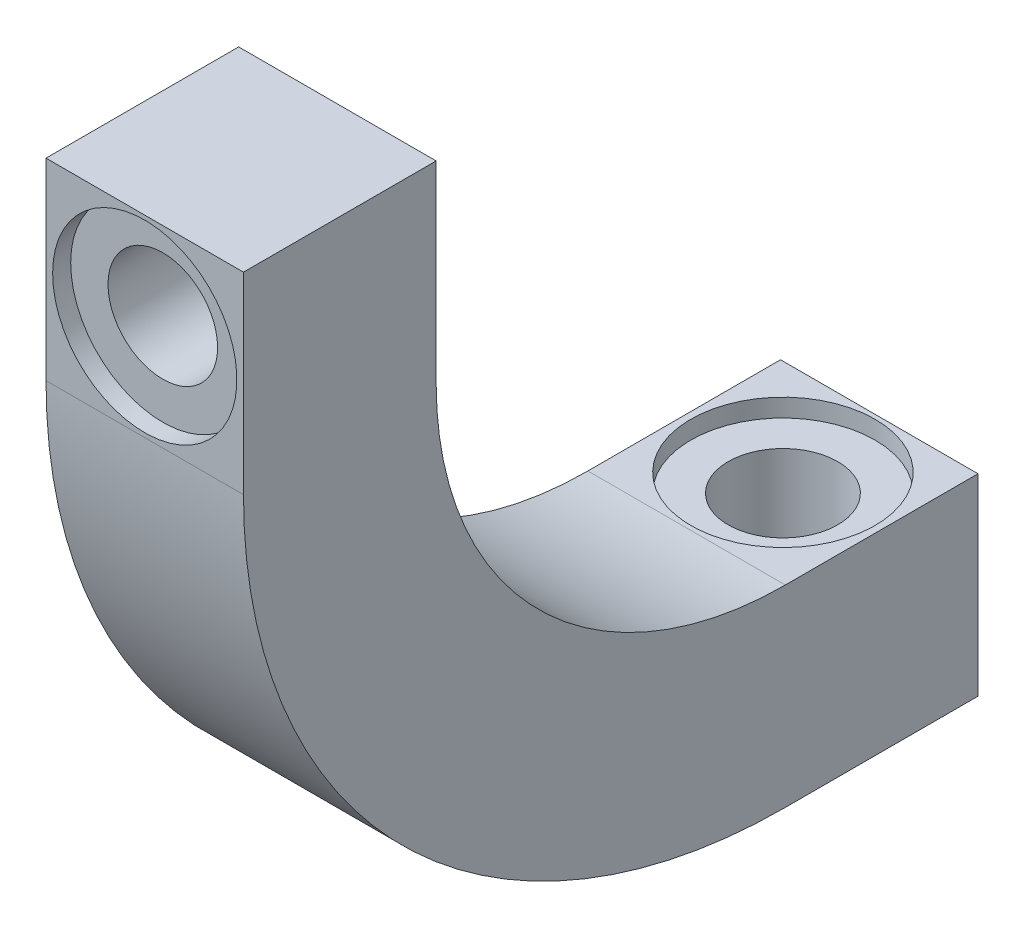
SolidWorks part; units mm, degrees
ref_plane "Front Plane" through (0, 0, 0) normal (0, 0, 1) x (1, 0, 0)
ref_plane "Top Plane" through (0, 0, 0) normal (0, 1, 0) x (1, 0, 0)
ref_plane "Right Plane" through (0, 0, 0) normal (1, 0, 0) x (0, 0, -1)
ref_axis "Z" through (0, 0, 22.75) along (0, 0, -1)
sketch "Sketch4" plane through (0, 0, 0) normal (0, 0, 1) x (1, 0, 0)
  circle A0 centre (0, 0) radius 17.5 construction
  dimension "D1" = 35
sketch "Sketch5" plane through (0, 0, 0) normal (1, 0, 0) x (0, 0, -1)
  line L0 (-18.5, 4) -> (-18.5, 0)
  line L1 (-18.5, 0) -> (-18.5, -4)
  line L2 (-26.5, -4) -> (-26.5, 4)
  line L6 (-26.5, 4) -> (-18.5, 4)
  line L12 (-22.75, 0) -> (-13.0351, 0) construction
  line L13 (0, 0) -> (-14.9091, -14.9091) construction
  line L14 (0, 0) -> (7.0065, 0) construction
  line L15 (0, -18.5) -> (-4, -18.5)
  line L16 (4, -18.5) -> (0, -18.5)
  line L17 (-4, -26.5) -> (4, -26.5)
  line L18 (4, -26.5) -> (4, -18.5)
  circle A0 centre (0, 0) radius 14 construction
  arc A1 (-18.5, -4) -> (-4, -18.5) centre (-4, -4) ccw
  arc A2 (-26.5, -4) -> (-4, -26.5) centre (-4, -4) ccw
  point P2 (9.4307, -21)
  point P4 (0, -2.1363)
  dimension "D1" = 28
  dimension "D4" = 4
  dimension "D2" = 45
  dimension "D3" = 8
  dimension "D5" = 18.5
sketch "Sketch6" plane through (0, 0, 0) normal (0, 1, 0) x (1, 0, 0)
  circle A0 centre (0, 0) radius 17.5 construction
  dimension "D1" = 35
extrude "Boss-Extrude1" add sketch "Sketch5" along normal blind 4.1 and the other way blind 4.1
sketch "Sketch7" plane through (0, 0, 0) normal (0, 0, 1) x (1, 0, 0)
  circle A0 centre (0, 0) radius 1.75
  dimension "D1" = 3.5
extrude "Cut-Extrude1" cut sketch "Sketch7" along normal through all
sketch "Sketch8" plane through (0, 0, 0) normal (0, 1, 0) x (1, 0, 0)
  circle A0 centre (0, 0) radius 1.75
  dimension "D1" = 3.5
extrude "Cut-Extrude2" cut sketch "Sketch8" against normal through all
ref_axis "Y" through (0, -9.3489, 0) along (0, -1, 0)
sketch "Sketch11" plane through (0, -18.5, 0) normal (0, -1, 0) x (1, 0, 0)
  circle A0 centre (0, 0) radius 2.275
  dimension "D1" = 4.55
extrude "Cut-Extrude6" cut sketch "Sketch11" along normal blind 6
sketch "Sketch12" plane through (0, 0, 26.5) normal (0, 0, 1) x (1, 0, 0)
  circle A0 centre (0, 0) radius 2.275
  dimension "D1" = 4.55
extrude "Cut-Extrude7" cut sketch "Sketch12" against normal blind 6
sketch "Sketch13" plane through (0, -18.5, 0) normal (0, -1, 0) x (1, 0, 0)
  circle A0 centre (0, 0) radius 3.825
  dimension "D1" = 7.65
extrude "Cut-Extrude8" cut sketch "Sketch13" along normal blind 0.75
sketch "Sketch14" plane through (0, 0, 26.5) normal (0, 0, -1) x (1, 0, 0)
  circle A0 centre (0, 0) radius 3.825
  dimension "D1" = 7.65
extrude "Cut-Extrude10" cut sketch "Sketch14" along normal blind 0.75
ref_plane "Plane1" through (0, -18.5, 0) normal (0, 1, 0) x (1, 0, 0)
ref_axis "CX" through (0, -18.5, 4.4) along (0, 0, -1)
ref_plane "Plane2" through (0, 0, 0) normal (0, 0, -1) x (0, 1, 0)
ref_plane "Plane3" through (0, 0, 0) normal (1, 0, 0) x (0, 0, -1)
ref_axis "CZ" through (0, -8.7018, 0) along (0, -1, 0)
ref_axis "CY" through (-0.6471, -18.5, 0) along (1, 0, 0)
ref_point "CO"
equation "\"rbracket-width\"= \"L2Thickness\" + 0.2"
equation "\"EyeCaptureRadius\"= ( \"EyeDiameter\" + \"EyeClearance\" ) / 2"
equation "\"rbracket_planetocenterline_dist\"= \"BasePlaneDistance\""
equation "\"EyeDiameter\" = 35"
equation "\"BasePlaneDistance\" = \"EyeDiameter\"/2+19.84"
equation "\"EyeClearance\" = 2"
equation "\"D1@Sketch4\"=\"EyeDiameter\""
equation "\"D1@Sketch6\"=\"EyeDiameter\""
equation "\"D1@Boss-Extrude1\"=\"rbracket-width\"/2"
equation "\"D2@Boss-Extrude1\"=\"rbracket-width\"/2"
equation "\"L2Thickness\" = 8"
equation "\"D3@Sketch5\"=\"L2Thickness\""
equation "\"D5@Sketch5\"=(\"EyeDiameter\"+\"EyeClearance\")/2"
equation "\"BearingThickness\"= 6"
equation "\"BearingOD\"=4.5"
equation "\"OuterBearingProudDistance\"= 0"
equation "\"D1@Cut-Extrude7\"=\"BearingThickness\"-\"OuterBearingProudDistance\""
equation "\"D1@Cut-Extrude6\"=\"BearingThickness\" - \"OuterBearingProudDistance\""
equation "\"D1@Sketch11\"=\"BearingOD\" + \"PrinterFilamentThickness\"*\"ApplyPrinterOffset\"/2"
equation "\"D1@Sketch12\"= \"BearingOD\" + \"PrinterFilamentThickness\" *\"ApplyPrinterOffset\" / 2"
equation "\"FlangeOD\"=7.5"
equation "\"FlangeThickness\"= 0.75"
equation "\"D1@Sketch14\"=\"FlangeOD\" + \"PrinterFilamentThickness\"*1.5 * \"ApplyPrinterOffset\""
equation "\"D1@Cut-Extrude10\"=\"FlangeThickness\""
equation "\"PrinterFilamentThickness\"= 0.1'For setting distances for things like pressfits"
equation "\"ApplyPrinterOffset\"= 1'Set to 0 for line-to-line. Set to 1 for applying guestimate dimensions to make the printer produce good parts"
equation "\"D1@Sketch13\"=\"FlangeOD\" + \"PrinterFilamentThickness\"*1.5 * \"ApplyPrinterOffset\""
